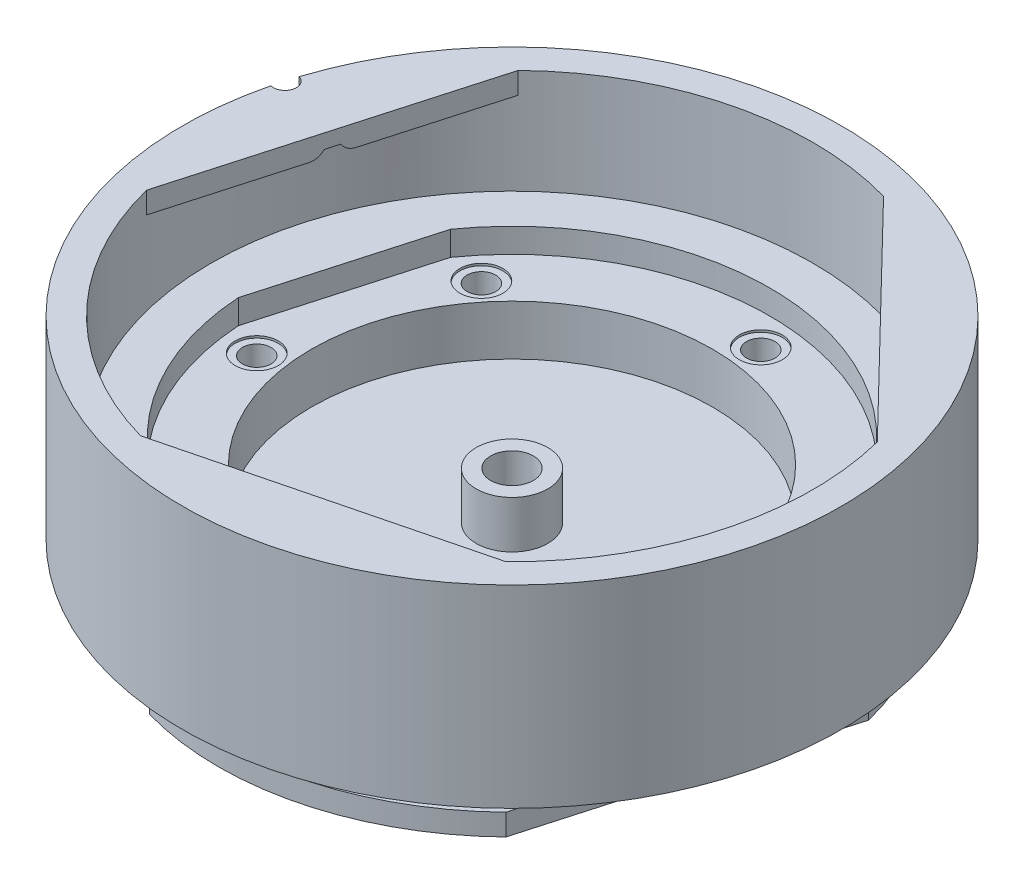
SolidWorks part; units mm, degrees
ref_plane "Front" through (0, 0, 0) normal (0, 0, 1) x (1, 0, 0)
ref_plane "Top" through (0, 0, 0) normal (0, 1, 0) x (1, 0, 0)
ref_plane "Right" through (0, 0, 0) normal (1, 0, 0) x (0, 0, -1)
sketch "Sketch1" plane through (0, 0, 0) normal (0, 1, 0) x (1, 0, 0)
  circle A0 centre (0, 0) radius 20.5
extrude "Boss-Extrude1" add sketch "Sketch1" along normal blind 1.5
sketch "Sketch2" plane through (0, 1.5, 0) normal (0, 1, 0) x (1, 0, 0)
  line L0 (-12.1923, 12.5538) -> (-12.889, 13.2712)
  line L1 (-16.9681, -4.2819) -> (-17.9377, -4.5266)
  line L2 (16.9681, 4.2819) -> (17.9377, 4.5266)
  line L3 (4.7758, 16.8357) -> (5.0487, 17.7978)
  line L4 (-4.7758, -16.8357) -> (-5.0487, -17.7978)
  line L5 (12.1923, -12.5538) -> (12.889, -13.2712)
  line L6 (-14.2824, 14.7059) -> (5.5945, 19.7219)
  line L7 (19.8769, 5.016) -> (14.2824, -14.7059)
  line L8 (-19.8769, -5.016) -> (-5.5945, -19.7219)
  line L9 (0, 0) -> (-14.2824, 14.7059) construction
  arc A0 (-19.8769, -5.016) -> (-5.5945, -19.7219) centre (0, 0) ccw
  arc A1 (-12.889, 13.2712) -> (-17.9377, -4.5266) centre (0, 0) ccw
  arc A2 (-12.1923, 12.5538) -> (-16.9681, -4.2819) centre (0, 0) ccw
  arc A3 (17.9377, 4.5266) -> (5.0487, 17.7978) centre (0, 0) ccw
  arc A4 (16.9681, 4.2819) -> (4.7758, 16.8357) centre (0, 0) ccw
  arc A5 (-5.0487, -17.7978) -> (12.889, -13.2712) centre (0, 0) ccw
  arc A6 (-4.7758, -16.8357) -> (12.1923, -12.5538) centre (0, 0) ccw
  arc A7 (14.2824, -14.7059) -> (19.8769, 5.016) centre (0, 0) ccw
  arc A8 (5.5945, 19.7219) -> (-14.2824, 14.7059) centre (0, 0) ccw
  point P13 (0, 0)
  dimension "D2" = 3
  dimension "D1" = 60
extrude "Cut-Extrude1" cut sketch "Sketch2" against normal blind 11
sketch "Sketch3" plane through (0, 1.5, 0) normal (0, 1, 0) x (1, 0, 0)
  circle A1 centre (0, 0) radius 17.5
extrude "Boss-Extrude2" add sketch "Sketch3" along normal blind 2
sketch "Sketch4" plane through (0, 3.5, 0) normal (0, 1, 0) x (1, 0, 0)
  circle A1 centre (0, 0) radius 23
extrude "Boss-Extrude3" add sketch "Sketch4" along normal blind 1
sketch "Sketch5" plane through (0, 4.5, 0) normal (0, 1, 0) x (1, 0, 0)
  circle A0 centre (0, 0) radius 23
  circle A1 centre (0, 0) radius 21
extrude "Boss-Extrude4" add sketch "Sketch5" along normal blind 11
sketch "Sketch6" plane through (0, 15.5, 0) normal (0, 1, 0) x (1, 0, 0)
  line L0 (0, 0) -> (-4.4043, 17.4529) construction
  line L2 (0, 0) -> (17.3168, -4.9122) construction
  line L5 (0, 0) -> (-12.9125, -12.5407) construction
  line L6 (14.6308, -15.0646) -> (-5.7309, -20.2029)
  line L7 (-20.3617, -5.1383) -> (-14.6308, 15.0646)
  line L8 (5.7309, 20.2029) -> (20.3617, 5.1383)
  circle A1 centre (0, 0) radius 23
  arc A4 (14.6308, -15.0646) -> (20.3617, 5.1383) centre (0, 0) ccw
  arc A5 (-20.3617, -5.1383) -> (-5.7309, -20.2029) centre (0, 0) ccw
  arc A6 (5.7309, 20.2029) -> (-14.6308, 15.0646) centre (0, 0) ccw
  point P14 (0, 0)
  point P18 (0, 0)
  point P22 (0, 0)
  dimension "D1" = 3
extrude "Boss-Extrude6" add sketch "Sketch6" along normal blind 1.5
sketch "Sketch7" plane through (0, 1.5, 0) normal (0, 1, 0) x (1, 0, 0)
  line L0 (0, 0) -> (4.2819, -16.9681) construction
  line L1 (4.0555, -18.05) -> (4.494, -20.0014)
  line L2 (4.9946, -17.813) -> (5.5346, -19.7388)
  arc A0 (-4.7758, -16.8357) -> (12.1923, -12.5538) centre (0, 0) ccw construction
  arc A1 (4.494, -20.0014) -> (5.5346, -19.7388) centre (0, 0) ccw
  arc A3 (4.0555, -18.05) -> (4.9946, -17.813) centre (0, 0) ccw
  dimension "D1" = 1.5
extrude "Boss-Extrude7" add sketch "Sketch7" along normal blind 0.8
fillet "Fillet3" radius 0.4 2 edges at (5.2646, 2.3, 18.7759) (4.2747, 2.3, 19.0257) first distance on face at (5.2646, 1.9, 18.7759) first distance on face at (4.2747, 1.9, 19.0257)
pattern_circular "CirPattern4" count 3 over 360 about axis through (0, 3.5, 0) along (0, 1, 0) of "Boss-Extrude7", "Fillet3"
ref_plane "Plane1" through (0, 15, 0) normal (0, 1, 0) x (1, 0, 0)
sketch "草图1" plane through (0, 17, 0) normal (0, 1, 0) x (1, 0, 0)
  line L0 (0, 0) -> (-12.5538, -12.1923) construction
  line L1 (0, 0) -> (-4.2819, 16.9681) construction
  line L2 (0, 0) -> (16.8357, -4.7758) construction
  circle A0 centre (0, 0) radius 18 construction
  circle A1 centre (0, 0) radius 17.5 construction
  circle A2 centre (0, 0) radius 18
  circle A3 centre (0, 0) radius 17
  point P9 (0, 0)
  dimension "D1" = 3
ref_plane "基准面1" through (0, 15, 0) normal (0, 1, 0) x (1, 0, 0)
sketch "草图9" plane through (0, 15, 0) normal (0, 1, 0) x (1, 0, 0)
  line L0 (0, 0) -> (5.016, -19.8769) construction
  line L3 (15.4424, 14.2314) -> (12.8687, 11.8595)
  line L4 (14.6764, 15.0201) -> (12.2303, 12.5167)
  arc A0 (4.494, -20.0014) -> (5.5346, -19.7388) centre (0, 0) ccw construction
  arc A5 (12.8687, 11.8595) -> (12.2303, 12.5167) centre (0, 0) ccw
  arc A6 (15.4424, 14.2314) -> (14.6764, 15.0201) centre (0, 0) ccw
  point P15 (0, 0)
extrude "切除-拉伸14" cut sketch "草图9" against normal blind 1 and the other way blind 1
fillet "圆角4" radius 1 2 edges at (14.4102, 15.5, -13.2802) (13.6954, 15.5, -14.0162)
pattern_circular "阵列(圆周)2" count 3 over 360 about axis through (0, 17, 0) along (0, 1, 0) of "切除-拉伸14", "圆角4"
sketch "草图15" plane through (0, 4.5, 0) normal (0, 1, 0) x (1, 0, 0)
  line L0 (0, 0) -> (-4.2819, 16.9681) construction
  circle A0 centre (0, 0) radius 21
  circle A5 centre (0, 0) radius 14
extrude "凸台-拉伸6" add sketch "草图15" along normal blind 3.5
sketch "草图16" plane through (0, 4.5, 0) normal (0, 1, 0) x (1, 0, 0)
  circle A0 centre (0, 0) radius 2.5
extrude "凸台-拉伸7" add sketch "草图16" along normal blind 3.3
sketch "草图17" plane through (0, 7.8, 0) normal (0, 1, 0) x (1, 0, 0)
  circle A0 centre (0, 0) radius 1.49
extrude "切除-拉伸17" cut sketch "草图17" against normal blind 32
sketch "草图20" plane through (0, 8, 0) normal (0, 1, 0) x (1, 0, 0)
  circle A0 centre (0, 0) radius 21
  circle A1 centre (0, 0) radius 18
extrude "凸台-拉伸8" add sketch "草图20" along normal blind 1.7
sketch "草图21" plane through (0, 8, 0) normal (0, 1, 0) x (1, 0, 0)
  line L0 (0, 0) -> (16.6631, -4.7268) construction
  line L2 (0, 0) -> (-7.1059, -25.0502) construction
  circle A0 centre (-15.6614, -2.1579) radius 1.5
  circle A1 centre (-6.9509, -14.2656) radius 1.5
  circle A2 centre (12.1955, -10.06) radius 1.5
  circle A3 centre (15.6614, 2.1579) radius 1.5
  circle A4 centre (1.575, 15.7905) radius 1.5
  circle A5 centre (-12.1955, 10.06) radius 1.5
  circle A6 centre (0, 0) radius 1.49 construction
  circle A7 centre (1.4334, -0.4066) radius 0.5 construction
  dimension "D1" = 14.478
  dimension "D3" = 2.794
  dimension "D5" = 14.478
  dimension "D2" = 6.35
  dimension "D4" = 15.621
  dimension "D6" = 6.35
extrude "切除-拉伸18" cut sketch "草图21" against normal blind 0.15
sketch "草图22" plane through (0, 7.85, 0) normal (0, 1, 0) x (1, 0, 0)
  line L0 (0, 0) -> (16.9497, -4.8081) construction
  circle A1 centre (-15.6614, -2.1579) radius 1
  circle A2 centre (-6.9509, -14.2656) radius 1
  circle A3 centre (12.1955, -10.06) radius 1
  circle A4 centre (15.6614, 2.1579) radius 1
  circle A5 centre (1.575, 15.7905) radius 1
  circle A6 centre (-12.1955, 10.06) radius 1
extrude "切除-拉伸19" cut sketch "草图22" against normal blind 10
sketch "草图24" plane through (0, 17, 0) normal (0, 1, 0) x (1, 0, 0)
  line L0 (0, 0) -> (-17.4962, 4.9631) construction
  circle A0 centre (-22.127, 6.2767) radius 0.8
  circle A1 centre (0, 0) radius 23 construction
extrude "切除-拉伸20" cut sketch "草图24" against normal blind 20
sketch "草图25" plane through (0, 8, 0) normal (0, 1, 0) x (1, 0, 0)
  line L0 (0, 0) -> (-25.762, 7.3079) construction
  line L1 (-14.689, 10.4035) -> (-17.9638, -1.141)
  arc A0 (-14.689, 10.4035) -> (-17.9638, -1.141) centre (0, 0) ccw
extrude "凸台-拉伸9" add sketch "草图25" along normal blind 1.7
